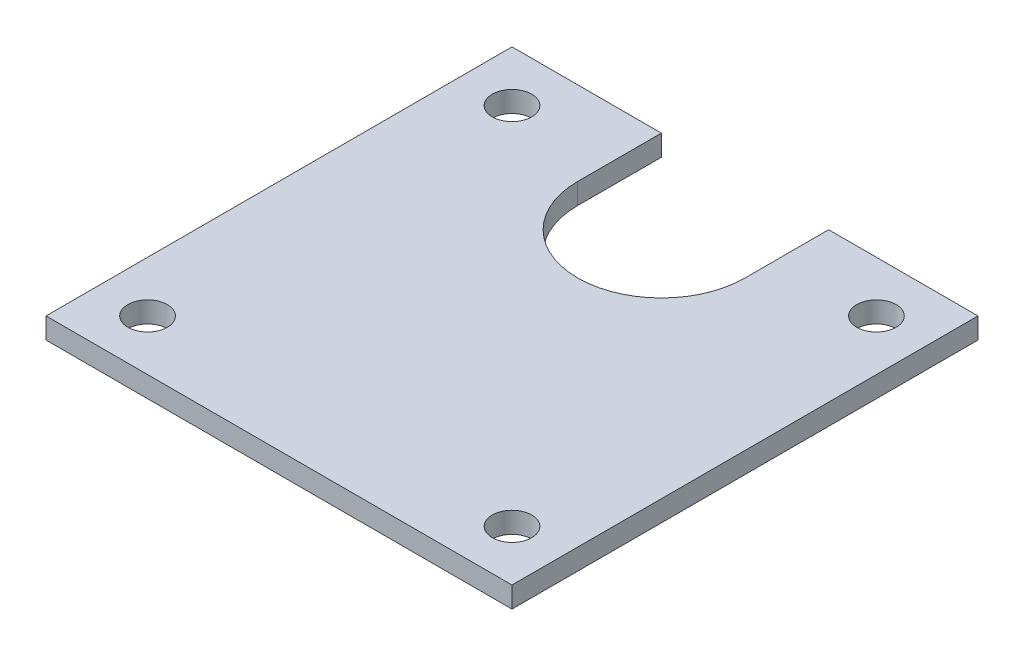
SolidWorks part; units mm, degrees
ref_plane "Front Plane" through (0, 0, 0) normal (0, 0, 1) x (1, 0, 0)
ref_plane "Top Plane" through (0, 0, 0) normal (0, 1, 0) x (1, 0, 0)
ref_plane "Right Plane" through (0, 0, 0) normal (1, 0, 0) x (0, 0, -1)
sketch "Sketch1" plane through (0, 0, 0) normal (0, 1, 0) x (1, 0, 0)
  line L0 (0, 19.5) -> (0, -19.5) construction
  line L1 (-19.5, 19.5) -> (19.5, 19.5)
  line L2 (-19.5, 19.5) -> (-19.5, -19.5)
  line L3 (-19.5, -19.5) -> (19.5, -19.5)
  line L4 (19.5, 19.5) -> (19.5, -19.5)
  line L5 (-19.5, 19.5) -> (19.5, -19.5) construction
  line L6 (-19.5, -19.5) -> (19.5, 19.5) construction
  line L7 (-19.5, 35.2) -> (-19.5, -19.5) construction
  circle A0 centre (-15.25, 15.25) radius 1.65
  circle A1 centre (15.25, 15.25) radius 1.65
  circle A2 centre (-15.25, -15.25) radius 1.65
  circle A3 centre (15.25, -15.25) radius 1.65
  circle A4 centre (15.25, 15.25) radius 1.65 construction
  circle A5 centre (15.25, -15.25) radius 1.65 construction
  circle A6 centre (-15.25, -15.25) radius 1.65 construction
  circle A7 centre (-15.25, 15.25) radius 1.65 construction
  point P0 (0, 0)
extrude "Shape" add sketch "Sketch1" along normal blind 1.75
sketch "Sketch2" plane through (0, 1.75, 0) normal (0, 1, 0) x (1, 0, 0)
  line L0 (0, 19.5) -> (0, -19.5) construction
  line L1 (-7, 12.5) -> (-7, 19.5)
  line L2 (7, 12.5) -> (7, 19.5)
  line L5 (19.5, 19.5) -> (-19.5, 19.5) construction
  line L6 (-19.5, -19.5) -> (19.5, -19.5) construction
  circle A0 centre (0, 12.5) radius 7
  line M4 (19.5, 19.5) -> (-19.5, 19.5)
  dimension "D1" = 14
extrude "Camera cut" cut sketch "Sketch2" against normal up to next contours L0 A0 | A0 L0 | A0 L2 M4 | A0 L1 M4 region at (2.9709, 1.75, -12.5) region at (5.4364, 1.75, -17.9364) region at (-2.9709, 1.75, -12.5) region at (-5.4364, 1.75, -17.9364)
